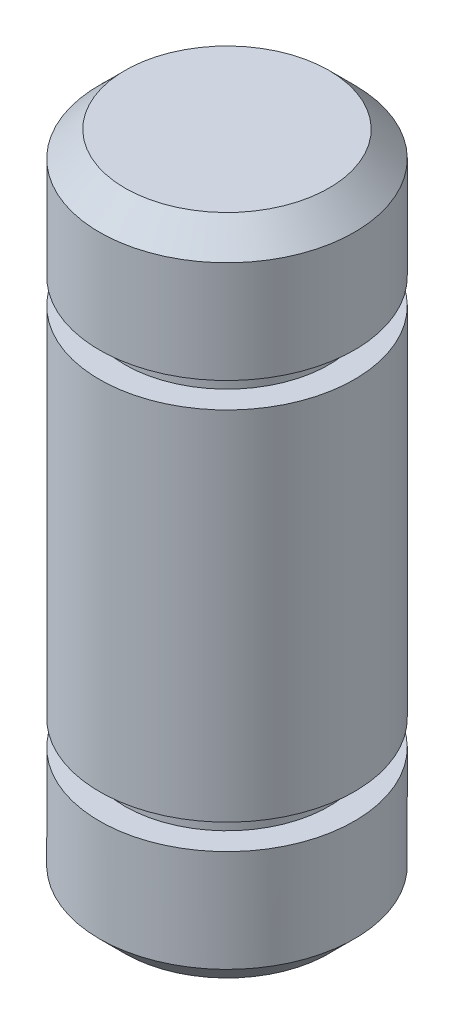
SolidWorks part; units mm, degrees
ref_plane "Front Plane" through (0, 0, 0) normal (0, 0, 1) x (1, 0, 0)
ref_plane "Top Plane" through (0, 0, 0) normal (0, 1, 0) x (1, 0, 0)
ref_plane "Right Plane" through (0, 0, 0) normal (1, 0, 0) x (0, 0, -1)
sketch "Sketch1" plane through (0, 0, 0) normal (0, 1, 0) x (1, 0, 0)
  circle A0 centre (0, 0) radius 5
  dimension "D1" = 10
extrude "Boss-Extrude1" add sketch "Sketch1" along normal blind 26
chamfer "Chamfer1" distance 1 angle 45 2 edges at (0, 0, 5) (0, 26, 5)
sketch "Sketch2" plane through (0, 0, 0) normal (0, -1, 0) x (1, 0, 0)
  circle A0 centre (0, 0) radius 4
  circle A1 centre (0, 0) radius 6
  dimension "D1" = 12
  dimension "D2" = 8
extrude "Cut-Extrude1" cut sketch "Sketch2" against normal blind 1 from offset 5 offset against normal yes
extrude "Cut-Extrude2" cut sketch "Sketch2<2>" against normal blind 1 from offset 20 offset against normal yes
sketch "Sketch2<2>" plane through (0, 0, 0) normal (0, -1, 0) x (1, 0, 0) same geometry as "Sketch2"
